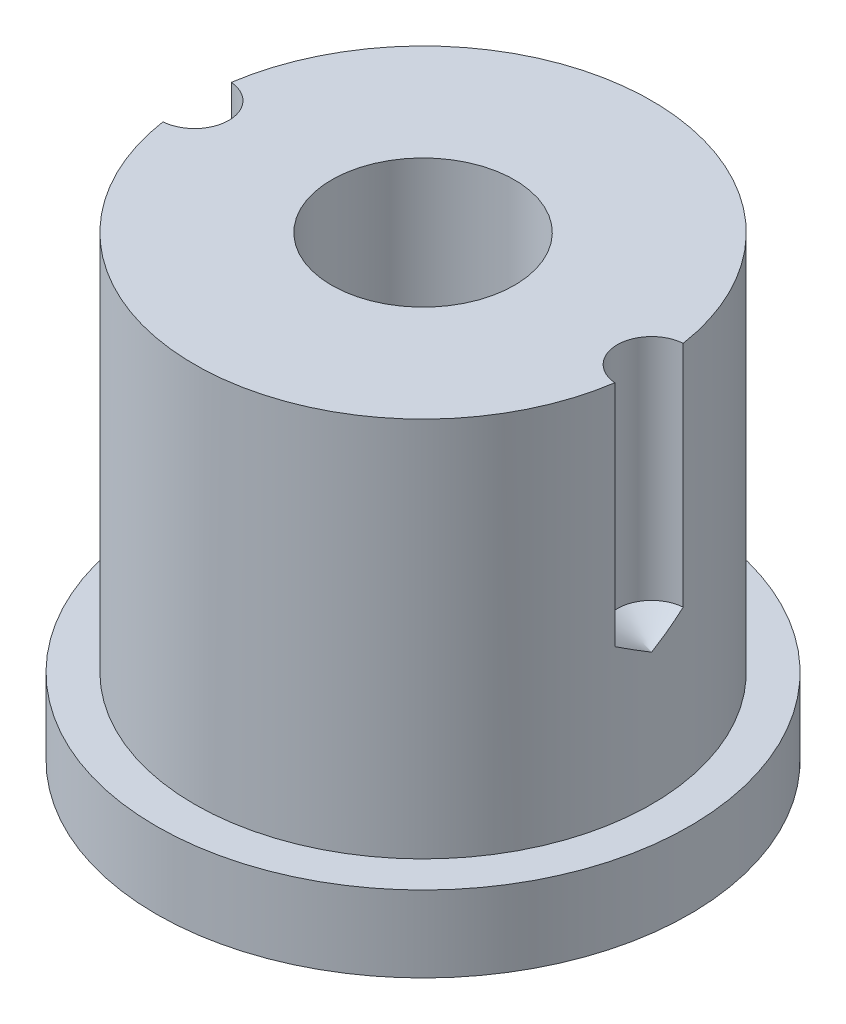
SolidWorks part; units mm, degrees
material "Commercial Bronze, UNS C22000 (90-10 Bronze)"
ref_plane "Front Plane" through (0, 0, 0) normal (0, 0, 1) x (1, 0, 0)
ref_plane "Top Plane" through (0, 0, 0) normal (0, 1, 0) x (1, 0, 0)
ref_plane "Right Plane" through (0, 0, 0) normal (1, 0, 0) x (0, 0, -1)
sketch "Sketch1" plane through (0, 0, 0) normal (0, 1, 0) x (1, 0, 0)
  circle A0 centre (0, 0) radius 35
  dimension "D1" = 70
extrude "Boss-Extrude1" add sketch "Sketch1" along normal blind 10
sketch "Sketch2" plane through (0, 10, 0) normal (0, 1, 0) x (1, 0, 0)
  circle A0 centre (0, 0) radius 30
  dimension "D1" = 60
extrude "Boss-Extrude2" add sketch "Sketch2" along normal blind 50
sketch "Sketch3" plane through (0, 60, 0) normal (0, 1, 0) x (1, 0, 0)
  circle A0 centre (0, 0) radius 12
  dimension "D1" = 24
extrude "Cut-Extrude1" cut sketch "Sketch3" against normal through all
hole_wizard "Ø8.0mm Dowel Hole1" positions "Sketch4" profile "Sketch5" hole size "Ø8.0" standard "ISO"
sketch "Sketch4" plane through (0, 60, 0) normal (0, 1, 0) x (1, 0, 0)
  circle A0 centre (0, 0) radius 30 construction
  circle A1 centre (0, 0) radius 30 construction
  point P0 (-30, 0)
  point P4 (30, 0)
sketch "Sketch5" plane through (-30, 60, 0) normal (1, 0, 0) x (0, 0, 1)
  line L0 (0, 0) -> (0, 32.7039)
  line L1 (0, 32.7039) -> (4.5, 30)
  line L2 (4.5, 30) -> (4.5, 0)
  line L5 (4.5, 0) -> (0, 0)
  line L10 (0, 32.7039) -> (-4.5, 30) construction
  line L11 (0, -6.35) -> (0, 107.95) construction
  dimension "Hole Dia." = 9
  dimension "Hole Depth" = 30
  dimension "Drill Angle" = 118
